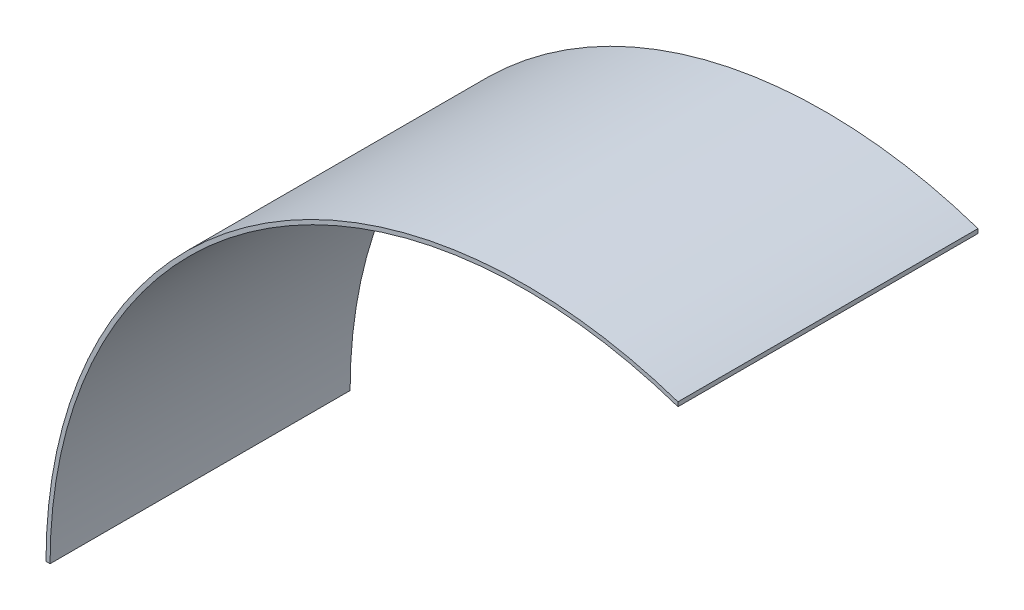
SolidWorks part; units mm, degrees
material "Plain Carbon Steel"
ref_plane "Front Plane" through (0, 0, 0) normal (0, 0, 1) x (1, 0, 0)
ref_plane "Top Plane" through (0, 0, 0) normal (0, 1, 0) x (1, 0, 0)
ref_plane "Right Plane" through (0, 0, 0) normal (1, 0, 0) x (0, 0, -1)
sketch "Sketch1" plane through (0, 0, 0) normal (0, 0, 1) x (1, 0, 0)
  line L0 (0, 0) -> (0, -179.3189) construction
  line L2 (0, 0) -> (101.5936, 0) construction
  line L3 (57.15, 113.7839) -> (57.15, -22.985) construction
  line L5 (57.15, 169.9681) -> (57.15, 168.3648)
  line L7 (0, 0) -> (-177.8, 0) construction
  line L10 (54.65, 169.1928) -> (54.65, 170.7883) construction
  line L25 (-179.3189, 0) -> (-177.8, 0)
  circle A0 centre (0, 0) radius 177.8 construction
  circle A1 centre (0, 0) radius 179.3189 construction
  arc A2 (-177.8, 0) -> (57.15, 168.3648) centre (0, 0) cw
  arc A3 (-179.3189, 0) -> (57.15, 169.9681) centre (0, 0) cw
  dimension "D1" = 355.6
  dimension "D2" = 358.6378
  dimension "D3" = 57.15
  dimension "D4" = 5
extrude "Inner Ring - Left Side" add sketch "Sketch1" along normal blind 112.268
